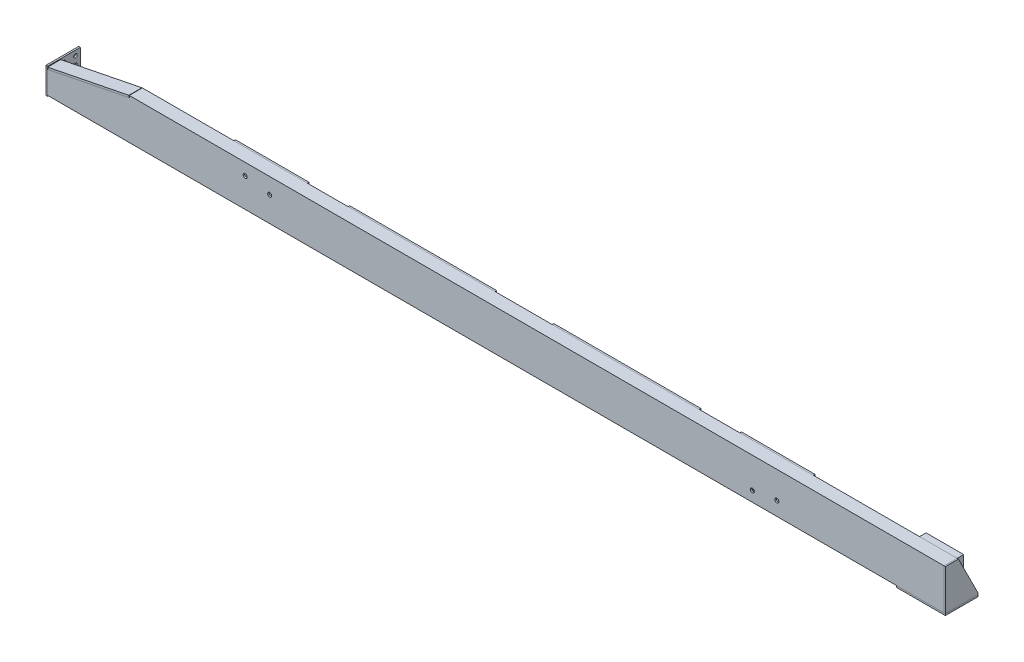
SolidWorks part; units mm, degrees
note: The reader was unsure of these and kept them because the rebuilt part matched: shared geometry of "草图26<2>".
material "普通碳钢"
ref_plane "前视基准面" through (0, 0, 0) normal (0, 0, 1) x (1, 0, 0)
ref_plane "上视基准面" through (0, 0, 0) normal (0, 1, 0) x (1, 0, 0)
ref_plane "右视基准面" through (0, 0, 0) normal (1, 0, 0) x (0, 0, -1)
sketch "草图1" plane through (0, 0, 0) normal (0, 0, 1) x (1, 0, 0)
  line L0 (-2745, 0) -> (2745, 0)
  dimension "D1" = 5490
other "槽钢 25B#(1)"
ref_plane "基准面1" through (-2745, 125, 0) normal (1, 0, 0) x (0, 0, -1)
sketch "草图11" plane through (-2745, 125, 0) normal (1, 0, 0) x (0, 0, -1)
  line L0 (0, -125) -> (80, -125)
  line L1 (80, -125) -> (80, -121.9796)
  line L2 (74.597, -116.0094) -> (19.8061, -110.5309)
  line L3 (9, -98.5904) -> (9, 98.5904)
  line L4 (19.8061, 110.5309) -> (74.597, 116.0094)
  line L5 (80, 121.9796) -> (80, 125)
  line L6 (80, 125) -> (0, 125)
  line L7 (0, 125) -> (0, -125)
  line L8 (44.5, 113) -> (44.5, -113) construction
  line L9 (0, 0) -> (9, 0) construction
  line L10 (44.5, 113) -> (44.5, 135) construction
  line L11 (44.5, 135) -> (80, 135) construction
  line L12 (80, 135) -> (80, 125) construction
  line L13 (44.5, 135) -> (9, 135) construction
  line L14 (9, 135) -> (9, 98.5904) construction
  arc A0 (19.8061, -110.5309) -> (9, -98.5904) centre (21, -98.5904) cw
  arc A1 (9, 98.5904) -> (19.8061, 110.5309) centre (21, 98.5904) cw
  arc A2 (80, -121.9796) -> (74.597, -116.0094) centre (74, -121.9796) ccw
  arc A3 (74.597, 116.0094) -> (80, 121.9796) centre (74, 121.9796) ccw
  point P2 (0, 0)
  point P19 (0, -125)
  point P20 (0, 125)
  point P22 (0, -125)
  point P23 (80, -125)
  point P24 (80, 125)
  point P26 (80, -116.5496)
  point P27 (21, 98.5904)
  point P28 (21, -98.5904)
  point P29 (80, 116.5496)
  dimension "D7" = 12
  dimension "D9" = 6
  dimension "D1" = 5.71
  dimension "D2" = 10
  dimension "D3" = 250
  dimension "D4" = 80
  dimension "D5" = 9
  dimension "D6" = 12
  dimension "D8" = 5.71
sketch "草图12" plane through (0, 0, 0) normal (0, 0, 1) x (1, 0, 0)
  line L0 (-2745, 250) -> (-2745, 137.7624)
  line L1 (-2745, 238) -> (-2745, 12) construction
  line L2 (-2745, 137.7624) -> (-2245, 237.7624)
  line L4 (-2245, 250) -> (-2745, 250)
  line L7 (-2745, 150) -> (-2245, 250) construction
  line L8 (-2305, 238) -> (-2733, 238) construction
  line L9 (-2733, 238) -> (-2733, 152.4) construction
  line L10 (-2733, 152.4) -> (-2305, 238) construction
  line L11 (-2245, 250) -> (-2245, 237.7624)
  line L13 (-2183.8118, 250) -> (-2745, 250) construction
  line L14 (-2745, 137.7624) -> (-2183.8118, 250) construction
  dimension "D1" = 12
  dimension "D2" = 500
  dimension "D3" = 100
extrude "切除-拉伸1" cut sketch "草图12" against normal up to vertex
sketch "草图13" plane through (0, 0, 0) normal (0, 0, 1) x (1, 0, 0)
  line L0 (-2745, 137.7624) -> (-2245, 237.7624) construction
  line L1 (-2742.6466, 138.233) -> (-2245, 237.7624)
  line L2 (-2247.3534, 249.5293) -> (-2245, 237.7624)
  line L3 (-2745, 150) -> (-2247.3534, 249.5293)
  line L4 (-2747.3534, 149.5293) -> (-2256.9785, 247.6043) construction
  line L5 (-2256.9785, 247.6043) -> (-2256.9785, 247.6043) construction
  line L6 (-2745, 150) -> (-2742.6466, 138.233)
  line L7 (-2745, 137.7624) -> (-2745, 0) construction
  line L9 (-2745, 137.7624) -> (-2245, 237.7624) construction
  line L10 (-2245.9996, 242.7603) -> (-2245, 237.7624) construction
  dimension "D1" = 12
extrude "凸台-拉伸1" add sketch "草图13" against normal up to vertex (80 mm away) separate body
fillet "圆角1" radius 8 1 edges at (-2493.8233, 187.9977, -80)
sketch "草图14" plane through (-2745, 0, 0) normal (-1, 0, 0) x (0, 0, 1)
  line L0 (0, 0) -> (-80, 0) construction
  line L1 (0, -5) -> (-200, -5)
  line L2 (0, -5) -> (0, 155)
  line L3 (0, 155) -> (-200, 155)
  line L4 (-200, -5) -> (-200, 155)
  line L5 (0, 137.7624) -> (0, 0) construction
  dimension "D1" = 200
  dimension "D2" = 160
  dimension "D3" = 5
extrude "凸台-拉伸2" add sketch "草图14" along normal blind 10 separate body
sketch "草图15" plane through (0, 0, -80) normal (0, 0, -1) x (-1, 0, 0)
  line L0 (-2745, 250) -> (2245, 250) construction
  line L1 (-1865, 250) -> (-1415, 250)
  line L2 (-1865, 250) -> (-1865, 0)
  line L3 (-1865, 0) -> (-1415, 0)
  line L4 (-1415, 250) -> (-1415, 0)
  line L5 (2745, 0) -> (-2745, 0) construction
  line L7 (-1165, 250) -> (-265, 250)
  line L8 (-1165, 250) -> (-1165, 0)
  line L9 (-1165, 0) -> (-265, 0)
  line L10 (-265, 250) -> (-265, 0)
  line L11 (85, 250) -> (985, 250)
  line L12 (85, 250) -> (85, 0)
  line L13 (85, 0) -> (985, 0)
  line L14 (985, 250) -> (985, 0)
  line L15 (1235, 250) -> (1685, 250)
  line L16 (1235, 250) -> (1235, 0)
  line L17 (1235, 0) -> (1685, 0)
  line L18 (1685, 250) -> (1685, 0)
  dimension "D1" = 2650
  dimension "D2" = 450
  dimension "D3" = 900
  dimension "D4" = 250
  dimension "D5" = 450
  dimension "D6" = 250
  dimension "D7" = 900
  dimension "D8" = 1060
extrude "凸台-拉伸3" add sketch "草图15" along normal blind 10 separate body
sketch "草图16" plane through (0, 0, 0) normal (0, -1, 0) x (1, 0, 0)
  line L0 (2753, 0) -> (2453, 0)
  line L1 (-2745, 0) -> (2745, 0) construction
  line L2 (2453, 0) -> (2453, -70)
  line L3 (2753, 0) -> (2753, -200)
  line L4 (2753, -200) -> (2653, -200)
  line L5 (2653, -200) -> (2453, -70)
  line L6 (2745, 0) -> (2745, -80) construction
  dimension "D1" = 8
  dimension "D2" = 300
  dimension "D3" = 200
  dimension "D4" = 70
  dimension "D5" = 100
extrude "凸台-拉伸4" add sketch "草图16" along normal blind 10 separate body
sketch "草图17" plane through (2745, 0, 0) normal (1, 0, 0) x (0, 0, -1)
  line L0 (0, 0) -> (200, 0)
  line L1 (200, 0) -> (200, 10)
  line L2 (200, 10) -> (80, 250)
  line L3 (80, 250) -> (0, 250) construction
  line L4 (80, 250) -> (0, 250)
  line L5 (0, 250) -> (0, 0)
  dimension "D1" = 10
extrude "凸台-拉伸5" add sketch "草图17" along normal blind 8 separate body
sketch "草图19" plane through (0, 0, -90) normal (0, 0, -1) x (-1, 0, 0)
  line L0 (1685, 0) -> (1685, 250) construction
  line L1 (1685, 250) -> (1235, 250) construction
  circle A0 centre (1535, 178) radius 12.5
  circle A1 centre (1385, 153) radius 12.5
  dimension "D1" = 150
  dimension "D3" = 25
  dimension "D4" = 72
  dimension "D5" = 25
  dimension "D6" = 25
  dimension "D2" = 150
extrude "切除-拉伸3" cut sketch "草图19" against normal up to surface (90 mm away)
sketch "草图18" plane through (0, 0, -90) normal (0, 0, -1) x (-1, 0, 0)
  line L0 (-2745, 250) -> (2245, 250) construction
  circle A0 centre (-1721, 84) radius 12.5
  circle A1 centre (-1571, 63) radius 12.5
  circle A2 centre (1535, 178) radius 12.5 construction
  dimension "D1" = 3106
  dimension "D4" = 25
  dimension "D6" = 25
  dimension "D3" = 187
  dimension "D2" = 150
  dimension "D5" = 21
extrude "切除-拉伸2" cut sketch "草图18" against normal up to surface (90 mm away)
sketch "草图20" plane through (0, 0, 0) normal (0, -1, 0) x (1, 0, 0)
  line L0 (-1535, -90) -> (-1535, 56.1712) construction
  line L1 (-1235, -90) -> (-1685, -90) construction
  line L2 (-1562, -80) -> (-1562, -8)
  line L3 (-1612, -80) -> (-1612, -8)
  line L4 (-1612, -80) -> (-1562, -80)
  line L5 (2745, -80) -> (-2745, -80) construction
  line L6 (-1612, -8) -> (-1562, -8)
  line L7 (-2745, 0) -> (2745, 0) construction
  line L9 (-1612, -90) -> (-1612, 56.1712) construction
  line L10 (-1562, -90) -> (-1562, 56.1712) construction
  dimension "D1" = 12.5
  dimension "D4" = 8
  dimension "D2" = 27
  dimension "D3" = 50
extrude "切除-拉伸4" cut sketch "草图20" against normal up to vertex (26.4096 mm away) up to point (-2745, 26.4096, -9)
sketch "草图21" plane through (0, 0, 0) normal (0, -1, 0) x (1, 0, 0)
  line L0 (1865, -80) -> (1415, -80) construction
  line L1 (1516, -80) -> (1696, -80)
  line L2 (1516, -80) -> (1516, -8)
  line L3 (1516, -8) -> (1696, -8)
  line L4 (1696, -80) -> (1696, -8)
  line L5 (-2745, 0) -> (2745, 0) construction
  line L6 (1571, -90) -> (1571, 39.993) construction
  line L7 (1865, -90) -> (1415, -90) construction
  dimension "D1" = 8
  dimension "D2" = 12.5
  dimension "D3" = 55
  dimension "D4" = 180
extrude "切除-拉伸5" cut sketch "草图21" against normal up to vertex (26.4096 mm away)
sketch "草图22" plane through (-2755, 0, 0) normal (-1, 0, 0) x (0, 0, 1)
  line L0 (-200, 75) -> (0, 75) construction
  line L2 (-200, 155) -> (-200, -5) construction
  line L3 (0, -5) -> (0, 155) construction
  line L4 (-100, 155) -> (-100, -5) construction
  line L5 (0, 155) -> (-200, 155) construction
  line L6 (-200, -5) -> (0, -5) construction
  line L7 (-170, 155) -> (-170, -5) construction
  line L8 (-30, 155) -> (-30, -5) construction
  line L9 (-200, 25) -> (0, 25) construction
  line L10 (-200, 125) -> (0, 125) construction
  line L11 (-200, 115) -> (0, 115) construction
  line L16 (-200, 35) -> (0, 35) construction
  circle A0 centre (-30, 115) radius 10.852
  circle A1 centre (-30, 35) radius 10.852
  circle A2 centre (-100, 25) radius 10.852
  circle A3 centre (-100, 75) radius 10.852
  circle A4 centre (-100, 125) radius 10.852
  circle A5 centre (-170, 125) radius 10.852
  circle A6 centre (-170, 75) radius 10.852
  circle A7 centre (-170, 25) radius 10.852
  dimension "D7" = 21.7041
  dimension "D1" = 70
  dimension "D2" = 70
  dimension "D3" = 50
  dimension "D4" = 50
  dimension "D5" = 40
  dimension "D6" = 40
extrude "切除-拉伸6" cut sketch "草图22" against normal up to next (10 mm away)
sketch "草图23" plane through (0, 0, -80) normal (0, 0, -1) x (-1, 0, 0)
  line L0 (-2753, 250) -> (-2745, 250) construction
  line L1 (-2745, 250) -> (-2515, 250)
  line L2 (-2745, 250) -> (-2745, 0)
  line L3 (-2745, 0) -> (-2515, 0)
  line L4 (-2515, 250) -> (-2515, 0)
  line L5 (-2745, 250) -> (2245, 250) construction
  line L6 (-2745, 0) -> (-1696, 0) construction
  line L7 (-2745, 26.4096) -> (-2745, 223.5904) construction
  line L8 (-2610, 250) -> (-2610, 8) construction
  line L9 (-2515, 129) -> (-2745, 129) construction
  line L10 (-2666.5685, 72.4315) -> (-2553.4315, 185.5685) construction
  line L11 (-2553.4315, 72.4315) -> (-2666.5685, 185.5685) construction
  circle A0 centre (-2610, 129) radius 68
  circle A1 centre (-2610, 129) radius 80 construction
  circle A2 centre (-2666.5685, 185.5685) radius 9.5
  circle A3 centre (-2553.4315, 185.5685) radius 9.5
  circle A4 centre (-2553.4315, 72.4315) radius 9.5
  circle A5 centre (-2666.5685, 72.4315) radius 9.5
  dimension "D2" = 136
  dimension "D3" = 160
  dimension "D4" = 45
  dimension "D6" = 19
  dimension "D7" = 19
  dimension "D8" = 19
  dimension "D9" = 19
  dimension "D1" = 230
  dimension "D5" = 45
  dimension "D10" = 95
  dimension "D11" = 121
extrude "凸台-拉伸6" add sketch "草图23" along normal blind 40 separate body
sketch "草图24" plane through (2515, 0, 0) normal (-1, 0, 0) x (0, 0, 1)
  line L0 (-120, 0) -> (-120, 250) construction
  line L1 (-120, 170.5) -> (-80, 170.5)
  line L2 (-120, 170.5) -> (-120, 105.5)
  line L3 (-120, 105.5) -> (-80, 105.5)
  line L4 (-80, 170.5) -> (-80, 105.5)
  line L5 (-80, 0) -> (-80, 250) construction
  line L6 (-120, 138) -> (-80, 138) construction
  line L7 (-120, 250) -> (-80, 250) construction
  dimension "D1" = 32.5
  dimension "D2" = 32.5
  dimension "D3" = 112
extrude "切除-拉伸7" cut sketch "草图24" against normal up to next
sketch "草图25" plane through (2515, 0, 0) normal (-1, 0, 0) x (0, 0, 1)
  line L0 (-80, 170.5) -> (-80, 250) construction
  line L1 (-80, 240) -> (-104, 240)
  line L2 (-80, 240) -> (-80, 10)
  line L3 (-80, 10) -> (-104, 10)
  line L4 (-104, 240) -> (-104, 10)
  line L5 (-120, 250) -> (-80, 250) construction
  line L6 (-120, 0) -> (-80, 0) construction
  point P6 (-92, 240)
  point P9 (-92, 10)
  dimension "D1" = 24
  dimension "D2" = 10
  dimension "D3" = 10
extrude "切除-拉伸8" cut sketch "草图25" against normal blind 220
fillet "圆角2" radius 20 2 edges at (2735, 10, -92) (2735, 240, -92)
fillet "圆角3" radius 10 2 edges at (2515, 105.5, -112) (2515, 170.5, -112)
sketch "草图26" plane through (0, 0, -0.8163) normal (0, 1, 0) x (1, 0, 0)
  line L0 (2449.8558, 39.1837) -> (2731.3909, 39.1837) construction
  line L1 (2580.114, 139.1837) -> (2724.7875, 139.1837) construction
  line L2 (2745, -0.8163) -> (-2745, -0.8163) construction
  line L3 (2701, 30.1837) -> (2701, 180.0233) construction
  line L4 (2601, 25.3137) -> (2601, 156.8805) construction
  line L5 (2501, 25.3137) -> (2501, 90.9281) construction
  line L6 (2753, 199.1837) -> (2753, -0.8163) construction
  circle A0 centre (2701, 39.1837) radius 9
  circle A1 centre (2601, 39.1837) radius 9
  circle A2 centre (2501, 39.1837) radius 9
  circle A3 centre (2601, 139.1837) radius 9
  circle A4 centre (2701, 139.1837) radius 9
  dimension "D3" = 18
  dimension "D7" = 18
  dimension "D8" = 18
  dimension "D9" = 18
  dimension "D10" = 18
  dimension "D1" = 100
  dimension "D2" = 40
  dimension "D4" = 100
  dimension "D5" = 100
  dimension "D6" = 52
extrude "切除-拉伸9" cut sketch "草图26" against normal blind 10
extrude "切除-拉伸10" cut sketch "草图26<2>" along normal up to surface (13.3499 mm away)
sketch "草图26<2>" plane through (0, 0, -0.8163) normal (0, 1, 0) x (1, 0, 0) same geometry as "草图26"
sketch "草图27" plane through (0, 0, 0) normal (0, -1, 0) x (1, 0, 0)
  line L0 (1696, -80) -> (1696, -8) construction
  line L13 (1756, 0) -> (1756, -80) construction
  line L14 (2745, -30) -> (-2745, -30)
  line L15 (2745, -30) -> (-2745, -30) construction
  line L16 (2745, 0) -> (-2745, 0) construction
  line L17 (1865, -80) -> (1415, -80) construction
  line L19 (1799, 0) -> (1799, -80) construction
  line L20 (1713, 0) -> (1713, -80) construction
  circle A0 centre (1799, -30) radius 7
  circle A1 centre (1713, -30) radius 7
  dimension "D5" = 14
  dimension "D2" = 60
  dimension "D1" = 30
  dimension "D3" = 43
  dimension "D4" = 43
extrude "切除-拉伸11" cut sketch "草图27" against normal up to next
pattern_linear "阵列(线性)1" count 2 spacing 3460 along (-1, 0, 0) of "切除-拉伸11"
sketch "草图28" plane through (0, 0, 0) normal (0, -1, 0) x (1, 0, 0)
  line L0 (1316, -15) -> (1416, -15) construction
  line L1 (1416, -15) -> (1416, -65) construction
  line L2 (1416, -65) -> (1316, -65) construction
  line L3 (1316, -65) -> (1316, -15) construction
  line L4 (1516, -8) -> (1516, -80) construction
  line L5 (2745, 0) -> (-2745, 0) construction
  circle A0 centre (1316, -15) radius 5
  circle A1 centre (1416, -15) radius 5
  circle A2 centre (1316, -65) radius 5
  circle A3 centre (1416, -65) radius 5
  dimension "D5" = 10
  dimension "D1" = 100
  dimension "D2" = 50
  dimension "D3" = 100
  dimension "D4" = 15
extrude "切除-拉伸12" cut sketch "草图28" against normal up to next (26.4096 mm away)
fillet "圆角4" radius 5 5 edges at (2615, 10, -104) (2615, 240, -104) (2729.1421, 234.1421, -104) (2735, 125, -104) (2729.1421, 15.8579, -104)
sketch "草图29" plane through (0, 0, 0) normal (0, -1, 0) x (1, 0, 0)
  line L0 (-1380, -15) -> (-1380, -65) construction
  line L1 (-1380, -65) -> (-1280, -65) construction
  line L2 (-1280, -65) -> (-1280, -15) construction
  line L3 (-1280, -15) -> (-1380, -15) construction
  line L4 (2745, 0) -> (-2745, 0) construction
  line L5 (-1562, -80) -> (-1562, -8) construction
  circle A0 centre (-1380, -65) radius 5
  circle A1 centre (-1380, -15) radius 5
  circle A2 centre (-1280, -15) radius 5
  circle A3 centre (-1280, -65) radius 5
  dimension "D1" = 50
  dimension "D5" = 10
  dimension "D2" = 100
  dimension "D3" = 15
  dimension "D4" = 182
extrude "切除-拉伸13" cut sketch "草图29" against normal up to next (26.4096 mm away) contours A2 | A3 | A0 | A1
